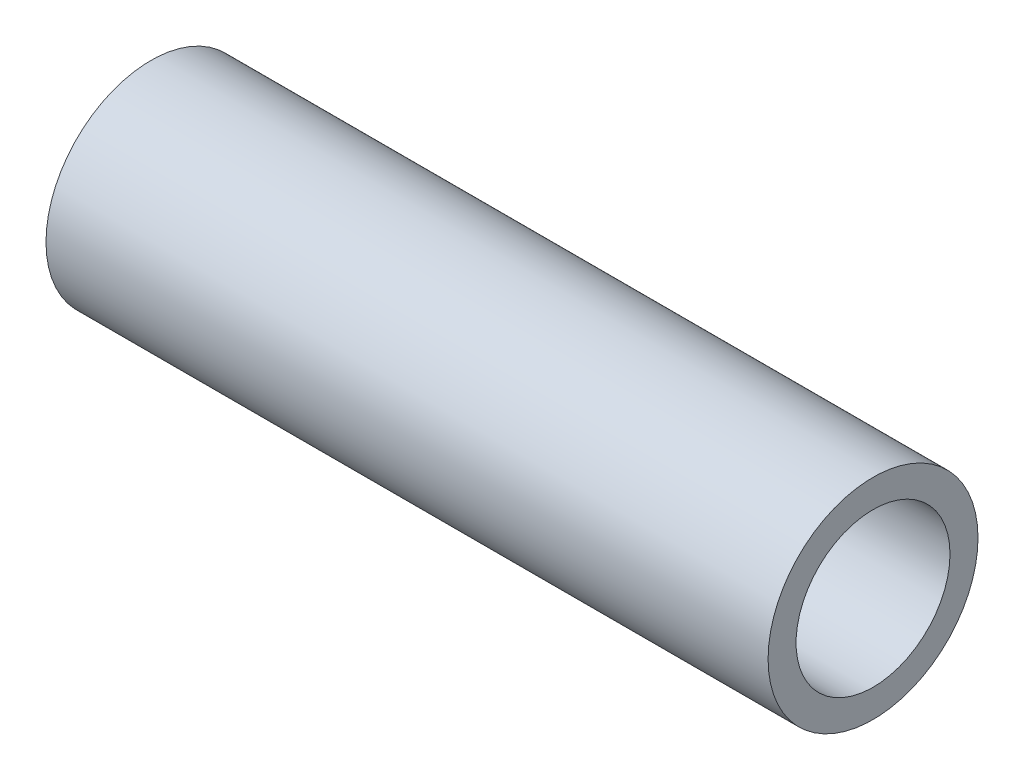
SolidWorks part; units mm, degrees
material "AISI 321 Annealed Stainless Steel (SS)"
ref_plane "Front Plane" through (0, 0, 0) normal (0, 0, 1) x (1, 0, 0)
ref_plane "Top Plane" through (0, 0, 0) normal (0, 1, 0) x (1, 0, 0)
ref_plane "Right Plane" through (0, 0, 0) normal (1, 0, 0) x (0, 0, -1)
sketch3d "3DSketch1"
  line L1 (-32.766, 0, 0) -> (32.766, 0, 0)
  point P5 (0, 0, 0)
  dimension "D1" = 65.532
sweep "Sweep-Thin1" add path "3DSketch1" circular profile diameter 19.05 parameters "D1"=2.54, "D3"=19.05
equation "\"D1@3DSketch1\"=2.58"
